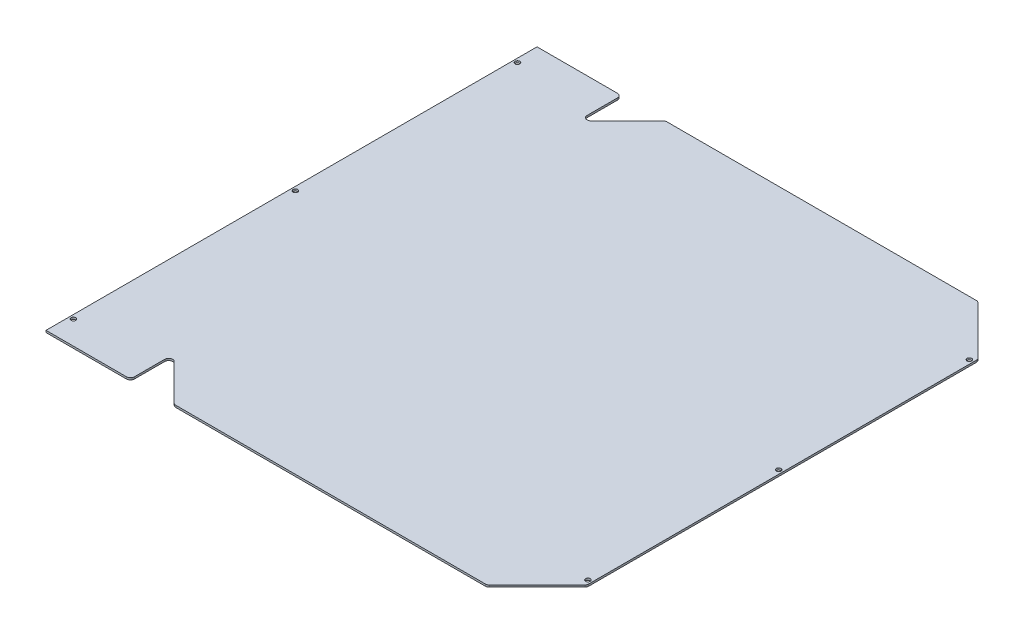
SolidWorks part; units mm, degrees
material "PC High Viscosity"
ref_plane "Front Plane" through (0, 0, 0) normal (0, 0, 1) x (1, 0, 0)
ref_plane "Top Plane" through (0, 0, 0) normal (0, 1, 0) x (1, 0, 0)
ref_plane "Right Plane" through (0, 0, 0) normal (1, 0, 0) x (0, 0, -1)
sketch "Sketch1" plane through (0, 0, 0) normal (0, 1, 0) x (1, 0, 0)
  line L0 (158.75, 199.39) -> (199.39, 158.75)
  line L1 (-199.39, 199.39) -> (199.39, 199.39)
  line L2 (-199.39, 199.39) -> (-199.39, -199.39)
  line L3 (-199.39, -199.39) -> (199.39, -199.39)
  line L4 (199.39, 199.39) -> (199.39, -199.39)
  line L5 (158.75, -199.39) -> (199.39, -158.75)
  line L6 (-130.81, 199.39) -> (-130.81, 163.83)
  line L7 (-130.81, 163.83) -> (-95.25, 199.39)
  line L9 (-130.81, -199.39) -> (-130.81, -163.83)
  line L10 (-130.81, -163.83) -> (-95.25, -199.39)
  point P0 (0, 0)
  point P6 (-199.39, 0)
  point P7 (196.215, 0)
  point P9 (0, 199.39)
  point P13 (-196.215, 0)
  point P27 (-196.215, -180.34)
  point P28 (196.215, 154.94)
  point P29 (196.215, -154.94)
  point P30 (-196.215, 180.34)
  dimension "D4" = 3.175
  dimension "D9" = 40.64
  dimension "D11" = 35.56
  dimension "D6" = 19.05
  dimension "D2" = 398.78
  dimension "D3" = 398.78
  dimension "D5" = 44.45
  dimension "D7" = 19.05
  dimension "D8" = 45
  dimension "D10" = 68.58
  dimension "D12" = 44.45
  dimension "D13" = 3.175
  dimension "D14" = 3.175
  dimension "D15" = 45
extrude "Boss-Extrude1" add sketch "Sketch1" against normal blind 1.5875
hole_wizard "#6 Clearance Hole1" positions "Sketch4" profile "Sketch5" hole size "#6" standard "ANSI Inch" end condition through all
sketch "Sketch4" plane through (0, -1.5875, 0) normal (0, -1, 0) x (-1, 0, 0)
  point P0 (196.215, 180.34)
  point P3 (196.215, -180.34)
  point P6 (-196.215, -154.94)
  point P9 (-196.215, 154.94)
  point P12 (196.215, 0)
  point P14 (-196.215, 0)
sketch "Sketch5" plane through (-196.215, -1.5875, -180.34) normal (1, 0, 0) x (0, 0, -1)
  line L0 (0, 0) -> (0, 1.5875)
  line L1 (0, 1.5875) -> (1.8986, 1.5875)
  line L2 (1.8986, 1.5875) -> (1.8986, 0)
  line L5 (1.8986, 0) -> (0, 0)
  line L11 (0, -6.35) -> (0, 107.95) construction
  dimension "Thru Hole Dia." = 3.7973
  dimension "Thru Hole Depth" = 1.5875
fillet "Fillet1" radius 3.175 10 edges at (158.75, -0.7937, -199.39) (199.39, -0.7937, -158.75) (199.39, -0.7937, 158.75) (158.75, -0.7937, 199.39) (-130.81, -0.7937, 163.83) (-130.81, -0.7937, 199.39) (-95.25, -0.7937, 199.39) (-95.25, -0.7937, -199.39) (-130.81, -0.7937, -199.39) (-130.81, -0.7937, -163.83)
